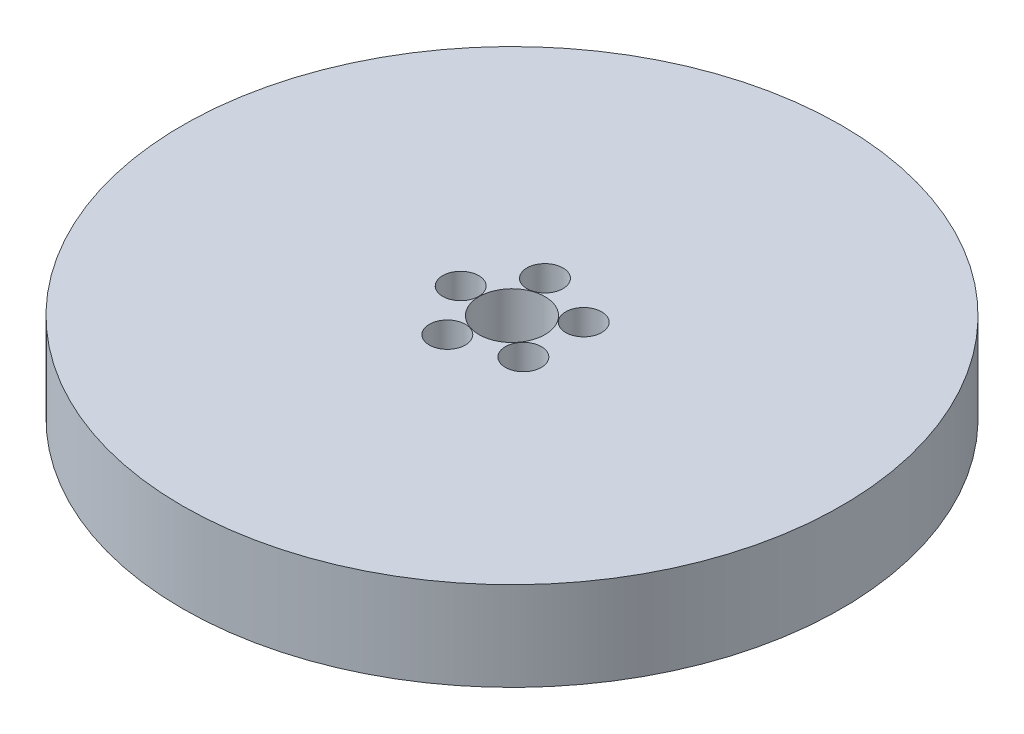
SolidWorks part; units mm, degrees
ref_plane "Front Plane" through (0, 0, 0) normal (0, 0, 1) x (1, 0, 0)
ref_plane "Top Plane" through (0, 0, 0) normal (0, 1, 0) x (1, 0, 0)
ref_plane "Right Plane" through (0, 0, 0) normal (1, 0, 0) x (0, 0, -1)
sketch "Sketch1" plane through (0, 0, 0) normal (0, 1, 0) x (1, 0, 0)
  circle A0 centre (0, 0) radius 100
  dimension "FLANGE_OD" = 200
extrude "Boss-Extrude1" add sketch "Sketch1" along normal blind 27
sketch "Sketch2" plane through (0, 0, 0) normal (0, 1, 0) x (1, 0, 0)
  circle A0 centre (0, 0) radius 10
  dimension "BORE_D" = 20
extrude "Cut-Extrude1" cut sketch "Sketch2" along normal through all
sketch "Sketch3" plane through (0, 27, 0) normal (0, 1, 0) x (1, 0, 0)
  circle A0 centre (0, 0) radius 15.5738 construction
  circle A1 centre (-15.5738, 0) radius 5.4662
  dimension "BOLT_D" = 10.9325
  dimension "BOLT_PCD" = 31.1477
extrude "Cut-Extrude2" cut sketch "Sketch3" against normal blind 23.4804
pattern_circular "CirPattern1" count 5 over 360 about axis through (0, 0, 0) along (0, 1, 0) of "Cut-Extrude2"
